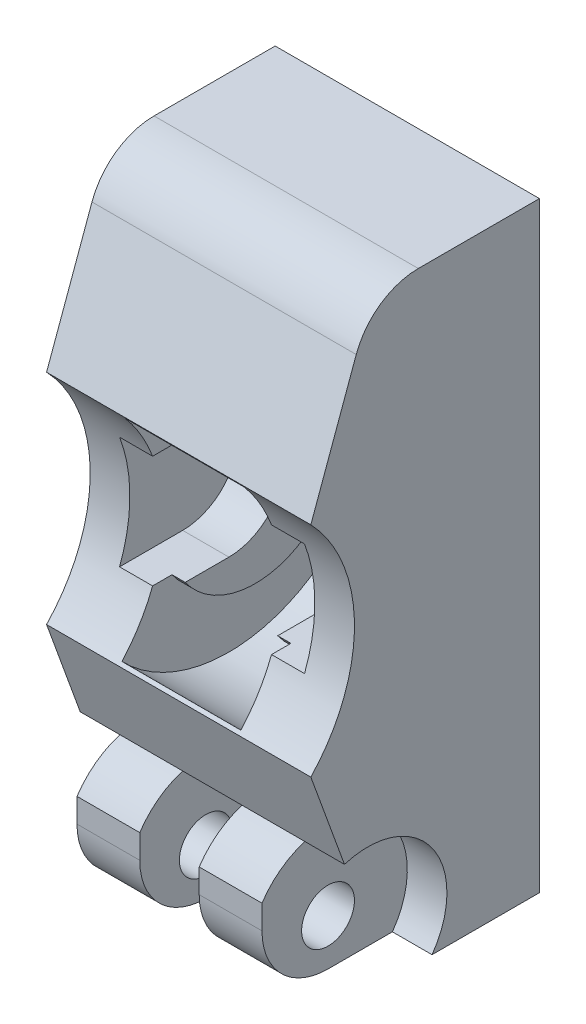
SolidWorks part; units mm, degrees
ref_plane "Plan de face" through (0, 0, 0) normal (0, 0, 1) x (1, 0, 0)
ref_plane "Plan de dessus" through (0, 0, 0) normal (0, 1, 0) x (1, 0, 0)
ref_plane "Plan de droite" through (0, 0, 0) normal (1, 0, 0) x (0, 0, -1)
sketch "Esquisse1" plane through (0, 0, 0) normal (1, 0, 0) x (0, 0, -1)
  line L0 (0, 22.75) -> (0, -22.75)
  line L1 (0, -22.75) -> (-18, -22.75)
  line L2 (-18, -22.75) -> (-18, -8.1)
  line L3 (-18, -8.1) -> (-18, 8.1)
  line L4 (-18, 8.1) -> (-12.6678, 22.75)
  line L5 (-12.6678, 22.75) -> (0, 22.75)
  line L6 (-18, 0) -> (0, 0) construction
  dimension "D1" = 45.5
  dimension "D3" = 70
  dimension "D4" = 16.2
  dimension "D5" = 18
extrude "Boss.-Extru.1" add sketch "Esquisse1" along normal blind 20
sketch "Esquisse2" plane through (0, 0, 0) normal (-1, 0, 0) x (0, 0, 1)
  line L0 (0, 22.75) -> (12.6678, 22.75) construction
  line L1 (0, 1.75) -> (26, 1.75) construction
  line L2 (0, -22.75) -> (0, 22.75) construction
  line L3 (18, 8.1) -> (18, -22.75) construction
  line L4 (18, -22.75) -> (0, -22.75) construction
  circle A0 centre (13, -19.25) radius 2
  circle A1 centre (26, 1.75) radius 12
  point P17 (0, 0)
  dimension "D4" = 21
  dimension "D5" = 4
  dimension "D2" = 24
  dimension "D1" = 3.5
  dimension "D3" = 5
  dimension "D8" = 26
extrude "Enlèv. mat.-Extru.1" cut sketch "Esquisse2" against normal up to next
sketch "Esquisse14" plane through (0, 0, 0) normal (-1, 0, 0) x (0, 0, 1)
  line L0 (10, 1.75) -> (0, 1.75) construction
  line L1 (0, -22.75) -> (0, 22.75) construction
  line L2 (10, 6) -> (14.7778, 6)
  line L3 (10, -2.5) -> (14.7778, -2.5)
  arc A0 (17.3022, 10.0173) -> (18, -7.1943) centre (26, 1.75) ccw construction
  arc A1 (10, 6) -> (10, -2.5) centre (10, 1.75) ccw
  arc A2 (17.3022, 10.0173) -> (18, -7.1943) centre (26, 1.75) ccw construction
  arc A3 (14.7778, 6) -> (14.7778, -2.5) centre (26, 1.75) ccw
  dimension "D1" = 8.5
  dimension "D2" = 10
extrude "Enlèv. mat.-Extru.7" cut sketch "Esquisse14" against normal blind 14 from offset 3 offset against normal yes
fillet "Congé1" radius 5 2 edges at (10, 22.75, 12.6678) (10, -22.75, 18)
ref_plane "Plan1" through (10, 0, 0) normal (-1, 0, 0) x (0, 0, 1)
sketch "Esquisse5" plane through (10, 0, 0) normal (-1, 0, 0) x (0, 0, 1)
  line L0 (9.0022, 12.7679) -> (16.301, 12.7679)
  line L1 (13.8653, 19.4601) -> (17.3022, 10.0173) construction
  line L2 (9.0022, -9.7321) -> (18, -9.7321)
  line L3 (18, -7.1943) -> (18, -17.75) construction
  line L6 (9.0022, 1.5179) -> (14.0022, 1.5179) construction
  circle A0 centre (9.0022, 1.5179) radius 11.25
  arc A1 (17.3022, 10.0173) -> (18, -7.1943) centre (26, 1.75) ccw construction
  dimension "D1" = 22.5
  dimension "D2" = 5
extrude "Enlèv. mat.-Extru.2" cut sketch "Esquisse5" against normal mid plane 9 contours A0 | A0 L0 | A0 L2 region at (10, 1.5179, 9.0022)
sketch "Esquisse8" plane through (5.5, 0, 0) normal (1, 0, 0) x (0, 0, -1)
  line L0 (-14.0099, 1.2639) -> (-8.0099, 1.2639) construction
  line L1 (-10, 6) -> (-12.4617, 6)
  line L2 (-10, 6) -> (-14.7778, 6) construction
  line L3 (-10, -2.5) -> (-13.3092, -2.5)
  line L4 (-14.7778, -2.5) -> (-10, -2.5) construction
  circle A0 centre (-8.0099, 1.2639) radius 6.5
  arc A1 (-18, -7.1943) -> (-17.3022, 10.0173) centre (-26, 1.75) ccw construction
  arc A3 (-10, 6) -> (-10, -2.5) centre (-10, 1.75) cw
  arc M15 (-10, 6) -> (-10, -2.5) centre (-10, 1.75) cw
  line M19 (-14.7778, 6) -> (-10, 6)
  line M20 (-10, -2.5) -> (-14.7778, -2.5)
  dimension "D1" = 13
  dimension "D2" = 6
extrude "Boss.-Extru.2" add sketch "Esquisse8" along normal blind 1 contours A0 M20 M19 M15 region at (5.5, 6.1756, 11.2309)
mirror "Symétrie1" about plane through (10, 0, 0) normal (-1, 0, 0) of "Boss.-Extru.2"
sketch "Esquisse11" plane through (10, 0, 0) normal (-1, 0, 0) x (0, 0, 1)
  circle A0 centre (13, -19.25) radius 6
  dimension "D1" = 12
extrude "Enlèv. mat.-Extru.3" cut sketch "Esquisse11" against normal mid plane 4.5
extrude "Enlèv. mat.-Extru.4" cut sketch "Esquisse11" against normal blind 3 from offset 10
extrude "Enlèv. mat.-Extru.5" cut sketch "Esquisse11<3>" against normal blind 3 from offset 7 offset against normal yes
sketch "Esquisse11<3>" plane through (10, 0, 0) normal (-1, 0, 0) x (0, 0, 1) same geometry as "Esquisse11"
sketch "Esquisse13" plane through (0, 0, 0) normal (-1, 0, 0) x (0, 0, 1)
  line L0 (18, -7.1943) -> (17.3022, -6.5173)
  line L1 (17.3022, -6.5173) -> (14.756, -13.5127)
  line L2 (18, -7.1943) -> (18, -15.9334)
  line L3 (17.3022, 10.0173) -> (17.3022, -6.5173) construction
  line L4 (8.1266, -22.75) -> (0, -22.75) construction
  arc A1 (18, -15.9334) -> (8.1266, -22.75) centre (13, -19.25) ccw construction
  arc A2 (14.756, -13.5127) -> (18, -15.9334) centre (13, -19.25) cw
  arc A4 (17.3022, 10.0173) -> (18, -7.1943) centre (26, 1.75) ccw construction
  dimension "D1" = 70
extrude "Enlèv. mat.-Extru.6" cut sketch "Esquisse13" against normal up to surface (20 mm away) up to face at (20, 1.4965, 9.7333)
